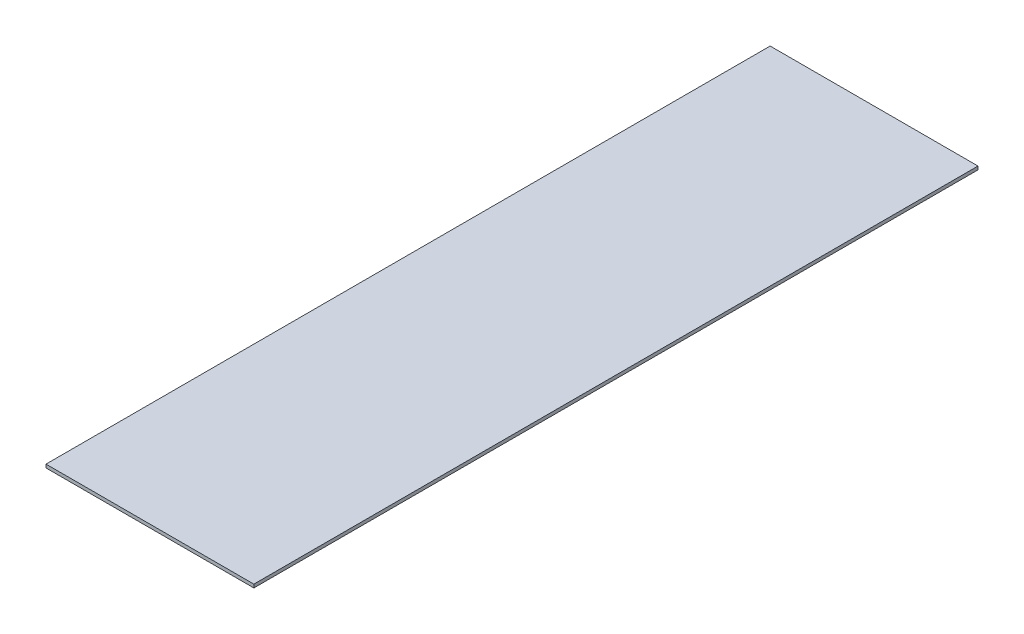
SolidWorks part; units mm, degrees
ref_plane "Front Plane" through (0, 0, 0) normal (0, 0, 1) x (1, 0, 0)
ref_plane "Top Plane" through (0, 0, 0) normal (0, 1, 0) x (1, 0, 0)
ref_plane "Right Plane" through (0, 0, 0) normal (1, 0, 0) x (0, 0, -1)
sketch "Sketch1" plane through (0, 0, 0) normal (0, 1, 0) x (1, 0, 0)
  line L1 (0, 0) -> (196.85, 0)
  line L2 (0, 0) -> (0, 685.8)
  line L3 (0, 685.8) -> (196.85, 685.8)
  line L4 (196.85, 0) -> (196.85, 685.8)
  dimension "D1" = 685.8
  dimension "D2" = 196.85
extrude "Boss-Extrude1" add sketch "Sketch1" along normal blind 3.175
